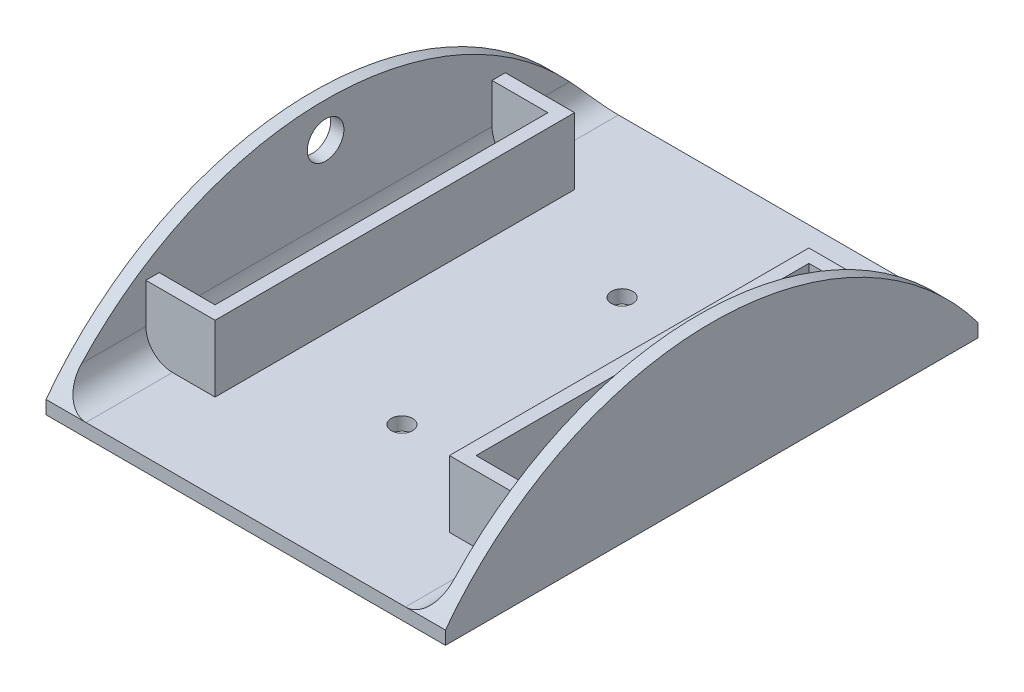
SolidWorks part; units mm, degrees
ref_plane "Front Plane" through (0, 0, 0) normal (0, 0, 1) x (1, 0, 0)
ref_plane "Top Plane" through (0, 0, 0) normal (0, 1, 0) x (1, 0, 0)
ref_plane "Right Plane" through (0, 0, 0) normal (1, 0, 0) x (0, 0, -1)
sketch "Sketch1" plane through (0, 0, 0) normal (0, 1, 0) x (1, 0, 0)
  line L1 (0, 0) -> (76.2, 0)
  line L2 (0, 0) -> (0, 101.6)
  line L3 (0, 101.6) -> (76.2, 101.6)
  line L4 (76.2, 0) -> (76.2, 101.6)
  dimension "D1" = 76.2
  dimension "D2" = 101.6
extrude "Base Extrude" add sketch "Sketch1" along normal blind 2.54
sketch "Sketch2" plane through (76.2, 0, 0) normal (1, 0, 0) x (0, 0, -1)
  line L2 (0, 2.54) -> (101.6, 2.54) construction
  line L3 (101.6, 2.54) -> (101.6, 0)
  line L4 (101.6, 0) -> (0, 0)
  line L5 (0, 0) -> (0, 2.54)
  arc A1 (0, 2.54) -> (101.6, 2.54) centre (50.8, -35.56) cw
  point P6 (50.8, 27.94)
  dimension "D1" = 25.4
extrude "Wall Extrude" add sketch "Sketch2" against normal blind 2.54 contours A1 L3 L4 L5
ref_plane "Wall Plane" through (38.1, 0, 0) normal (1, 0, 0) x (0, 0, -1)
mirror "Wall Mirror" about plane through (38.1, 0, 0) normal (1, 0, 0) of "Wall Extrude"
sketch "Sketch3" plane through (0, 0, 0) normal (-1, 0, 0) x (0, 0, 1)
  line L0 (-50.8, 27.94) -> (-50.8, -0.5285) construction
  circle A0 centre (-50.8, 21.2725) radius 3.4925
  arc A1 (0, 2.54) -> (-101.6, 2.54) centre (-50.8, -35.56) ccw construction
  dimension "D1" = 6.985
  dimension "D2" = 6.6675
extrude "Cut-Extrude1" cut sketch "Sketch3" against normal up to next
fillet "Fillet2" radius 5.08 2 edges at (2.54, 2.54, -50.8) (73.66, 2.54, -50.8)
sketch "Sketch4" plane through (0, 2.54, 0) normal (0, 1, 0) x (1, 0, 0)
  line L0 (38.1, 0) -> (38.1, 101.6) construction
  line L1 (0, 0) -> (76.2, 0) construction
  line L2 (76.2, 101.6) -> (0, 101.6) construction
  line L3 (38.1, 29.8) -> (38.1, 71.8) construction
  line L4 (76.2, 50.8) -> (0, 50.8) construction
  line L5 (76.2, 0) -> (76.2, 101.6) construction
  line L6 (0, 101.6) -> (0, 0) construction
  circle A0 centre (38.1, 71.8) radius 2.032
  circle A1 centre (38.1, 29.8) radius 2.032
  circle A2 centre (51.86, 90.1995) radius 2.032
  dimension "D1" = 4.064
  dimension "D2" = 42
extrude "Cut-Extrude2" cut sketch "Sketch4" against normal through all
sketch "Sketch5" plane through (0, 2.54, 0) normal (0, 1, 0) x (1, 0, 0)
  line L0 (2.54, 4.241) -> (2.54, 97.359) construction
  line L1 (13.208, 19.05) -> (2.54, 19.05)
  line L2 (13.208, 19.05) -> (13.208, 82.55)
  line L3 (13.208, 82.55) -> (2.54, 82.55)
  line L4 (2.54, 19.05) -> (2.54, 82.55)
  line L6 (15.748, 85.09) -> (2.54, 85.09)
  line L7 (15.748, 85.09) -> (15.748, 16.51)
  line L8 (15.748, 16.51) -> (2.54, 16.51)
  line L9 (2.54, 85.09) -> (2.54, 16.51)
  point P6 (13.208, 50.8)
  point P9 (2.54, 50.8)
  line M6 (7.62, 101.6) -> (7.62, 0)
  dimension "D1" = 63.5
  dimension "D2" = 2.54
  dimension "D3" = 2.54
  dimension "D4" = 68.58
  dimension "D5" = 10.668
extrude "Boss-Extrude1" add sketch "Sketch5" along normal blind 12.7 contours L8 L7 L6 L3 L2 L1 M6 | L6 L9 L3 M6 | L1 L9 L8 M6 region at (13.9085, 2.54, -50.8) region at (5.08, 2.54, -17.78) region at (5.08, 2.54, -83.82)
mirror "Mirror1" about plane through (38.1, 0, 0) normal (1, 0, 0) of "Boss-Extrude1"
